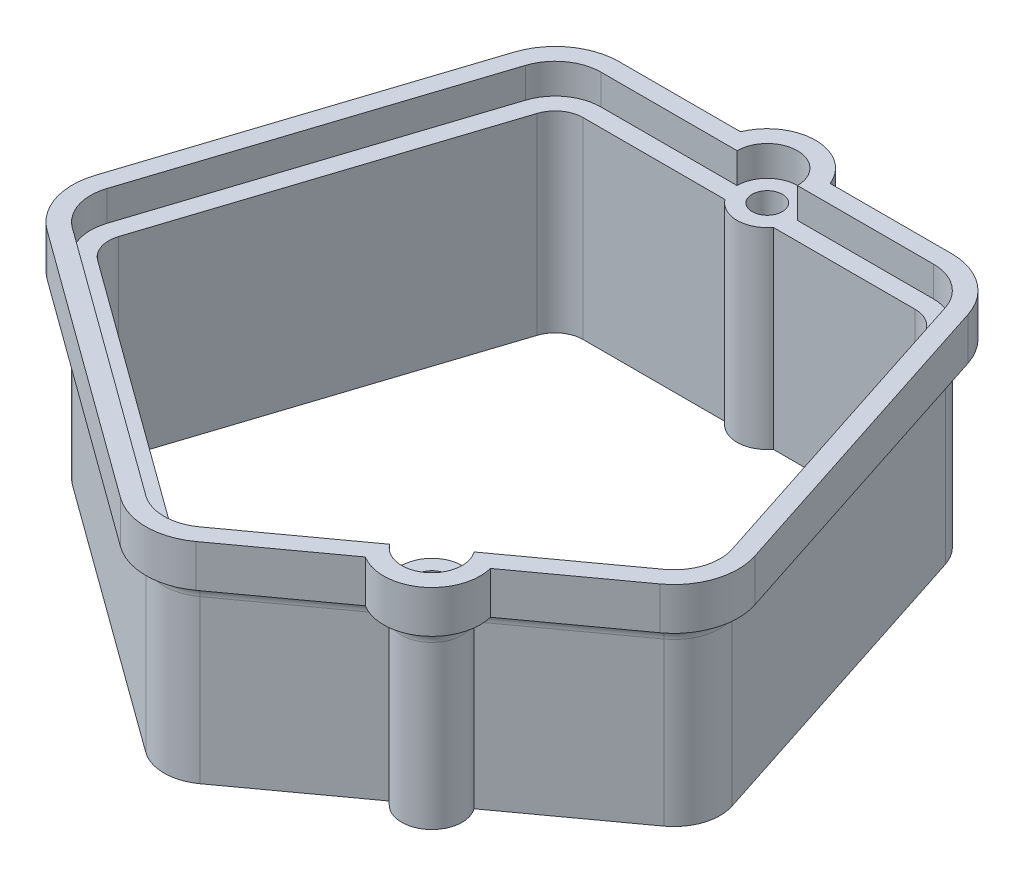
SolidWorks part; units mm, degrees
material "ABS"
ref_plane "Front Plane" through (0, 0, 0) normal (0, 0, 1) x (1, 0, 0)
ref_plane "Top Plane" through (0, 0, 0) normal (0, 1, 0) x (1, 0, 0)
ref_plane "Right Plane" through (0, 0, 0) normal (1, 0, 0) x (0, 0, -1)
sketch "Sketch1" plane through (0, 0, 0) normal (0, 1, 0) x (1, 0, 0)
  line L0 (-42.9604, -16.814) -> (1.5332, -49.1405)
  line L1 (6.9643, -49.1405) -> (25.975, -35.3284)
  line L2 (4.2488, 51.849) -> (4.2488, 50.849)
  line L3 (0.2488, 46.849) -> (-23.2498, 46.849)
  line L4 (-30.4968, 41.5837) -> (-47.4919, -10.7216)
  line L5 (-44.7237, -19.241) -> (-0.2302, -51.5675)
  line L6 (8.7277, -51.5675) -> (27.7384, -37.7554)
  line L7 (33.3256, -38.6403) -> (33.9134, -39.4494)
  line L8 (35.0196, -32.4654) -> (53.2213, -19.241)
  line L9 (55.9894, -10.7216) -> (38.9943, 41.5837)
  line L10 (31.7473, 46.849) -> (9.2488, 46.849)
  line L11 (32.4472, -30.6261) -> (51.4579, -16.814)
  line L12 (53.1362, -11.6487) -> (36.1412, 40.6567)
  line L13 (31.7473, 43.849) -> (8.2488, 43.849)
  line L14 (-23.2498, 43.849) -> (0.2488, 43.849)
  line L15 (-44.6387, -11.6487) -> (-27.6437, 40.6567)
  line L16 (-47.4919, -15.431) -> (47.4919, 15.431) construction
  line L17 (-44.6387, -14.504) -> (44.6387, 14.504) construction
  arc A0 (9.2488, 46.849) -> (4.2488, 51.849) centre (4.2488, 46.849) ccw
  arc A1 (4.2488, 50.849) -> (0.2488, 46.849) centre (4.2488, 46.849) ccw
  arc A2 (-23.2498, 46.849) -> (-30.4968, 41.5837) centre (-23.2498, 39.229) ccw
  arc A3 (-47.4919, -10.7216) -> (-44.7237, -19.241) centre (-40.2448, -13.0763) ccw
  arc A4 (-0.2302, -51.5675) -> (8.7277, -51.5675) centre (4.2488, -45.4028) ccw
  arc A5 (27.7384, -37.7554) -> (33.3256, -38.6403) centre (30.9745, -35.4043) ccw
  arc A6 (33.9134, -39.4494) -> (35.0196, -32.4654) centre (30.9745, -35.4043) ccw
  arc A7 (53.2213, -19.241) -> (55.9894, -10.7216) centre (48.7423, -13.0763) ccw
  arc A8 (38.9943, 41.5837) -> (31.7473, 46.849) centre (31.7473, 39.229) ccw
  arc A9 (-44.6387, -11.6487) -> (-42.9604, -16.814) centre (-40.2448, -13.0763) ccw
  arc A10 (1.5332, -49.1405) -> (6.9643, -49.1405) centre (4.2488, -45.4028) ccw
  circle A11 centre (30.9745, -35.4043) radius 2.5
  arc A12 (32.4472, -30.6261) -> (25.975, -35.3284) centre (30.9745, -35.4043) ccw
  arc A13 (51.4579, -16.814) -> (53.1362, -11.6487) centre (48.7423, -13.0763) ccw
  arc A14 (36.1412, 40.6567) -> (31.7473, 43.849) centre (31.7473, 39.229) ccw
  arc A15 (0.2488, 43.849) -> (8.2488, 43.849) centre (4.2488, 46.849) ccw
  circle A16 centre (4.2488, 46.849) radius 2.5
  arc A17 (-23.2498, 43.849) -> (-27.6437, 40.6567) centre (-23.2498, 39.229) ccw
  arc A36 (4.2488, 51.849) -> (-0.7512, 46.849) centre (4.2488, 46.849) ccw
  arc A37 (33.9134, -39.4494) -> (26.9294, -38.3432) centre (30.9745, -35.4043) cw
  point P58 (0, 0)
  point P60 (0, 0)
extrude "Boss-Extrude1" add sketch "Sketch1" along normal blind 40 contours L9 A8 L10 A0 L2 A1 L3 A2 L4 A3 L5 A4 L6 A5 L7 A6 L8 A7 A17 L14 A15 L13 A14 L12 A13 L11 A12 L1 A10 L0 A9 L15 A16 A11 | A37 L7 A5 L6 | L2 A36 L3 A1 region at (6.7388, 0, -49.339) region at (1.3722, 0, -49.7256) region at (30.3381, 0, 39.4223)
sketch "Sketch2" plane through (0, 40, 0) normal (0, 1, 0) x (1, 0, 0)
  line L1 (-30.4968, 41.5837) -> (-33.35, 42.5108)
  line L2 (-47.4919, -10.7216) -> (-50.345, -9.7946)
  line L3 (-33.35, 42.5108) -> (-50.345, -9.7946)
  line L5 (-23.2498, 46.849) -> (-23.2498, 49.849)
  line L8 (55.9894, -10.7216) -> (38.9943, 41.5837)
  line L9 (31.7473, 46.849) -> (9.2488, 46.849)
  line L10 (-0.7512, 46.849) -> (-23.2498, 46.849)
  line L13 (-30.4968, 41.5837) -> (-47.4919, -10.7216)
  line L21 (-44.7237, -19.241) -> (-0.2302, -51.5675)
  line L22 (8.7277, -51.5675) -> (26.9294, -38.3432)
  line L23 (35.0196, -32.4654) -> (53.2213, -19.241)
  line L24 (55.9894, -10.7216) -> (38.9943, 41.5837)
  line L25 (31.7473, 46.849) -> (9.2488, 46.849)
  line L26 (-0.7512, 46.849) -> (-23.2498, 46.849)
  line L27 (-30.4968, 41.5837) -> (-47.4919, -10.7216)
  line L28 (-44.7237, -19.241) -> (-0.2302, -51.5675)
  line L29 (8.7277, -51.5675) -> (26.9294, -38.3432)
  line L30 (35.0196, -32.4654) -> (53.2213, -19.241)
  line L31 (-23.2498, 49.849) -> (-3.1674, 49.849)
  line L33 (54.9846, -21.6681) -> (38.7377, -33.4722)
  line L34 (10.491, -53.9946) -> (26.738, -42.1905)
  line L35 (-1.9935, -53.9946) -> (-46.4871, -21.6681)
  line L36 (31.7473, 49.849) -> (11.665, 49.849)
  line L37 (41.8475, 42.5108) -> (58.8425, -9.7946)
  arc A0 (-3.1674, 49.849) -> (11.665, 49.849) centre (4.2488, 46.849) cw
  arc A1 (-33.35, 42.5108) -> (-23.2498, 49.849) centre (-23.2498, 39.229) cw
  arc A3 (-50.345, -9.7946) -> (-46.4871, -21.6681) centre (-40.2448, -13.0763) ccw
  arc A5 (41.8475, 42.5108) -> (31.7473, 49.849) centre (31.7473, 39.229) ccw
  arc A6 (58.8425, -9.7946) -> (54.9846, -21.6681) centre (48.7423, -13.0763) cw
  arc A21 (26.738, -42.1905) -> (38.7377, -33.4722) centre (30.9745, -35.4043) ccw
  arc A22 (-1.9935, -53.9946) -> (10.491, -53.9946) centre (4.2488, -45.4028) ccw
  arc A23 (38.9943, 41.5837) -> (31.7473, 46.849) centre (31.7473, 39.229) ccw
  arc A24 (9.2488, 46.849) -> (-0.7512, 46.849) centre (4.2488, 46.849) ccw
  arc A25 (-23.2498, 46.849) -> (-30.4968, 41.5837) centre (-23.2498, 39.229) ccw
  arc A26 (-47.4919, -10.7216) -> (-44.7237, -19.241) centre (-40.2448, -13.0763) ccw
  arc A27 (-0.2302, -51.5675) -> (8.7277, -51.5675) centre (4.2488, -45.4028) ccw
  arc A28 (26.9294, -38.3432) -> (35.0196, -32.4654) centre (30.9745, -35.4043) ccw
  arc A29 (53.2213, -19.241) -> (55.9894, -10.7216) centre (48.7423, -13.0763) ccw
  arc A30 (38.9943, 41.5837) -> (31.7473, 46.849) centre (31.7473, 39.229) ccw
  arc A31 (9.2488, 46.849) -> (-0.7512, 46.849) centre (4.2488, 46.849) ccw
  arc A32 (-23.2498, 46.849) -> (-30.4968, 41.5837) centre (-23.2498, 39.229) ccw
  arc A33 (-47.4919, -10.7216) -> (-44.7237, -19.241) centre (-40.2448, -13.0763) ccw
  arc A34 (-0.2302, -51.5675) -> (8.7277, -51.5675) centre (4.2488, -45.4028) ccw
  arc A35 (26.9294, -38.3432) -> (35.0196, -32.4654) centre (30.9745, -35.4043) ccw
  arc A36 (53.2213, -19.241) -> (55.9894, -10.7216) centre (48.7423, -13.0763) ccw
  line M62 (55.9894, -10.7216) -> (38.9943, 41.5837)
  arc M63 (38.9943, 41.5837) -> (31.7473, 46.849) centre (31.7473, 39.229) ccw
  line M64 (31.7473, 46.849) -> (9.2488, 46.849)
  arc M65 (9.2488, 46.849) -> (-0.7512, 46.849) centre (4.2488, 46.849) ccw
  line M66 (-0.7512, 46.849) -> (-23.2498, 46.849)
  arc M67 (-23.2498, 46.849) -> (-30.4968, 41.5837) centre (-23.2498, 39.229) ccw
  line M68 (-30.4968, 41.5837) -> (-47.4919, -10.7216)
  arc M69 (-47.4919, -10.7216) -> (-44.7237, -19.241) centre (-40.2448, -13.0763) ccw
  line M70 (-44.7237, -19.241) -> (-0.2302, -51.5675)
  arc M71 (-0.2302, -51.5675) -> (8.7277, -51.5675) centre (4.2488, -45.4028) ccw
  line M72 (8.7277, -51.5675) -> (26.9294, -38.3432)
  arc M73 (26.9294, -38.3432) -> (35.0196, -32.4654) centre (30.9745, -35.4043) ccw
  line M74 (35.0196, -32.4654) -> (53.2213, -19.241)
  arc M75 (53.2213, -19.241) -> (55.9894, -10.7216) centre (48.7423, -13.0763) ccw
  dimension "D5" = 3
  dimension "D2" = 3
  dimension "D3" = 3
  dimension "D1" = 0
extrude "Boss-Extrude2" add sketch "Sketch2" along normal blind 5 and the other way blind 2 contours L1 L3 L2 M68 | L35 A22 L34 A21 L33 A6 L37 A5 L36 A0 L31 L5 L2 A3 M66 M65 M64 M63 M62 M75 M74 M73 M72 M71 M70 M69 | A1 L1 L5 M67 region at (-40.4209, 40, -15.8946) region at (-28.3098, 40, -46.1935) region at (-48.9788, 40, 15.9142)
fillet "Fillet1" radius 3 14 edges at (20.498, 38, -46.849) (36.2262, 38, -45.3937) (47.4919, 38, -15.431) (55.9894, 38, 15.431) (-12.0005, 38, -46.849) (-27.7287, 38, -45.3937) (-38.9943, 38, -15.431) (-47.4919, 38, 15.431) (17.8285, 38, 44.9554) (4.2488, 38, 53.0228) (4.2488, 38, -51.849) (33.9134, 38, 39.4494) (44.1204, 38, 25.8532) (-22.477, 38, 35.4043)
sketch "Sketch3" plane through (0, 0, 0) normal (0, -1, 0) x (1, 0, 0)
  line L7 (-44.6387, 11.6487) -> (-27.6437, -40.6567)
  line L8 (1.5332, 49.1405) -> (-42.9604, 16.814)
  line L9 (25.975, 35.3284) -> (6.9643, 49.1405)
  line L10 (51.4579, 16.814) -> (32.4472, 30.6261)
  line L11 (36.1412, -40.6567) -> (53.1362, 11.6487)
  line L12 (8.2488, -43.849) -> (31.7473, -43.849)
  line L13 (-23.2498, -43.849) -> (0.2488, -43.849)
  line L14 (-44.6387, 11.6487) -> (-27.6437, -40.6567)
  line L15 (1.5332, 49.1405) -> (-42.9604, 16.814)
  line L16 (25.975, 35.3284) -> (6.9643, 49.1405)
  line L17 (51.4579, 16.814) -> (32.4472, 30.6261)
  line L18 (36.1412, -40.6567) -> (53.1362, 11.6487)
  line L19 (8.2488, -43.849) -> (31.7473, -43.849)
  line L20 (-23.2498, -43.849) -> (0.2488, -43.849)
  line L21 (38.9943, -41.5837) -> (55.9894, 10.7216)
  line L22 (53.2213, 19.241) -> (35.0196, 32.4654)
  line L23 (26.9294, 38.3432) -> (8.7277, 51.5675)
  line L24 (-0.2302, 51.5675) -> (-44.7237, 19.241)
  line L25 (-47.4919, 10.7216) -> (-30.4968, -41.5837)
  line L26 (-23.2498, -46.849) -> (-0.7512, -46.849)
  line L27 (9.2488, -46.849) -> (31.7473, -46.849)
  line L28 (38.9943, -41.5837) -> (55.9894, 10.7216)
  line L29 (53.2213, 19.241) -> (35.0196, 32.4654)
  line L30 (26.9294, 38.3432) -> (8.7277, 51.5675)
  line L31 (-0.2302, 51.5675) -> (-44.7237, 19.241)
  line L32 (-47.4919, 10.7216) -> (-30.4968, -41.5837)
  line L33 (-23.2498, -46.849) -> (-0.7512, -46.849)
  line L34 (9.2488, -46.849) -> (31.7473, -46.849)
  circle A1 centre (30.9745, 35.4043) radius 2.5
  circle A2 centre (30.9745, 35.4043) radius 2.5
  circle A3 centre (4.2488, -46.849) radius 2.5
  circle A4 centre (4.2488, -46.849) radius 2.5
  arc A7 (-27.6437, -40.6567) -> (-23.2498, -43.849) centre (-23.2498, -39.229) ccw
  arc A8 (-42.9604, 16.814) -> (-44.6387, 11.6487) centre (-40.2448, 13.0763) ccw
  arc A9 (6.9643, 49.1405) -> (1.5332, 49.1405) centre (4.2488, 45.4028) ccw
  arc A10 (25.975, 35.3284) -> (32.4472, 30.6261) centre (30.9745, 35.4043) ccw
  arc A11 (53.1362, 11.6487) -> (51.4579, 16.814) centre (48.7423, 13.0763) ccw
  arc A12 (31.7473, -43.849) -> (36.1412, -40.6567) centre (31.7473, -39.229) ccw
  arc A13 (8.2488, -43.849) -> (0.2488, -43.849) centre (4.2488, -46.849) ccw
  arc A14 (-27.6437, -40.6567) -> (-23.2498, -43.849) centre (-23.2498, -39.229) ccw
  arc A15 (-42.9604, 16.814) -> (-44.6387, 11.6487) centre (-40.2448, 13.0763) ccw
  arc A16 (6.9643, 49.1405) -> (1.5332, 49.1405) centre (4.2488, 45.4028) ccw
  arc A17 (25.975, 35.3284) -> (32.4472, 30.6261) centre (30.9745, 35.4043) ccw
  arc A18 (53.1362, 11.6487) -> (51.4579, 16.814) centre (48.7423, 13.0763) ccw
  arc A19 (31.7473, -43.849) -> (36.1412, -40.6567) centre (31.7473, -39.229) ccw
  arc A20 (8.2488, -43.849) -> (0.2488, -43.849) centre (4.2488, -46.849) ccw
  arc A25 (55.9894, 10.7216) -> (53.2213, 19.241) centre (48.7423, 13.0763) ccw
  arc A26 (35.0196, 32.4654) -> (26.9294, 38.3432) centre (30.9745, 35.4043) ccw
  arc A27 (8.7277, 51.5675) -> (-0.2302, 51.5675) centre (4.2488, 45.4028) ccw
  arc A28 (-44.7237, 19.241) -> (-47.4919, 10.7216) centre (-40.2448, 13.0763) ccw
  arc A29 (-30.4968, -41.5837) -> (-23.2498, -46.849) centre (-23.2498, -39.229) ccw
  arc A30 (-0.7512, -46.849) -> (9.2488, -46.849) centre (4.2488, -46.849) ccw
  arc A31 (31.7473, -46.849) -> (38.9943, -41.5837) centre (31.7473, -39.229) ccw
  arc A32 (55.9894, 10.7216) -> (53.2213, 19.241) centre (48.7423, 13.0763) ccw
  arc A33 (35.0196, 32.4654) -> (26.9294, 38.3432) centre (30.9745, 35.4043) ccw
  arc A34 (8.7277, 51.5675) -> (-0.2302, 51.5675) centre (4.2488, 45.4028) ccw
  arc A35 (-44.7237, 19.241) -> (-47.4919, 10.7216) centre (-40.2448, 13.0763) ccw
  arc A36 (-30.4968, -41.5837) -> (-23.2498, -46.849) centre (-23.2498, -39.229) ccw
  arc A37 (-0.7512, -46.849) -> (9.2488, -46.849) centre (4.2488, -46.849) ccw
  arc A38 (31.7473, -46.849) -> (38.9943, -41.5837) centre (31.7473, -39.229) ccw
  dimension "D1" = 0
  dimension "D2" = 0
  dimension "D3" = 0
  dimension "D4" = 0
extrude "Boss-Extrude3" add sketch "Sketch3" along normal blind 7
sketch "Sketch4" plane through (0, -7, 0) normal (0, -1, 0) x (1, 0, 0)
  line L7 (-23.2498, -43.849) -> (0.2488, -43.849)
  line L8 (-44.6387, 11.6487) -> (-27.6437, -40.6567)
  line L9 (1.5332, 49.1405) -> (-42.9604, 16.814)
  line L10 (25.975, 35.3284) -> (6.9643, 49.1405)
  line L11 (51.4579, 16.814) -> (32.4472, 30.6261)
  line L12 (36.1412, -40.6567) -> (53.1362, 11.6487)
  line L13 (8.2488, -43.849) -> (31.7473, -43.849)
  line L14 (-23.2498, -43.849) -> (0.2488, -43.849)
  line L15 (-44.6387, 11.6487) -> (-27.6437, -40.6567)
  line L16 (1.5332, 49.1405) -> (-42.9604, 16.814)
  line L17 (25.975, 35.3284) -> (6.9643, 49.1405)
  line L18 (51.4579, 16.814) -> (32.4472, 30.6261)
  line L19 (36.1412, -40.6567) -> (53.1362, 11.6487)
  line L20 (8.2488, -43.849) -> (31.7473, -43.849)
  line L21 (38.9943, -41.5837) -> (55.9894, 10.7216)
  line L22 (53.2213, 19.241) -> (35.0196, 32.4654)
  line L23 (26.9294, 38.3432) -> (8.7277, 51.5675)
  line L24 (-0.2302, 51.5675) -> (-44.7237, 19.241)
  line L25 (-47.4919, 10.7216) -> (-30.4968, -41.5837)
  line L26 (-23.2498, -46.849) -> (-0.7512, -46.849)
  line L27 (9.2488, -46.849) -> (31.7473, -46.849)
  line L28 (38.9943, -41.5837) -> (55.9894, 10.7216)
  line L29 (53.2213, 19.241) -> (35.0196, 32.4654)
  line L30 (26.9294, 38.3432) -> (8.7277, 51.5675)
  line L31 (-0.2302, 51.5675) -> (-44.7237, 19.241)
  line L32 (-47.4919, 10.7216) -> (-30.4968, -41.5837)
  line L33 (-23.2498, -46.849) -> (-0.7512, -46.849)
  line L34 (9.2488, -46.849) -> (31.7473, -46.849)
  circle A1 centre (30.9745, 35.4043) radius 2.5
  circle A2 centre (30.9745, 35.4043) radius 2.5
  circle A3 centre (4.2488, -46.849) radius 2.5
  circle A4 centre (4.2488, -46.849) radius 2.5
  arc A7 (-27.6437, -40.6567) -> (-23.2498, -43.849) centre (-23.2498, -39.229) ccw
  arc A8 (-42.9604, 16.814) -> (-44.6387, 11.6487) centre (-40.2448, 13.0763) ccw
  arc A9 (6.9643, 49.1405) -> (1.5332, 49.1405) centre (4.2488, 45.4028) ccw
  arc A10 (25.975, 35.3284) -> (32.4472, 30.6261) centre (30.9745, 35.4043) ccw
  arc A11 (53.1362, 11.6487) -> (51.4579, 16.814) centre (48.7423, 13.0763) ccw
  arc A12 (31.7473, -43.849) -> (36.1412, -40.6567) centre (31.7473, -39.229) ccw
  arc A13 (8.2488, -43.849) -> (0.2488, -43.849) centre (4.2488, -46.849) ccw
  arc A14 (-27.6437, -40.6567) -> (-23.2498, -43.849) centre (-23.2498, -39.229) ccw
  arc A15 (-42.9604, 16.814) -> (-44.6387, 11.6487) centre (-40.2448, 13.0763) ccw
  arc A16 (6.9643, 49.1405) -> (1.5332, 49.1405) centre (4.2488, 45.4028) ccw
  arc A17 (25.975, 35.3284) -> (32.4472, 30.6261) centre (30.9745, 35.4043) ccw
  arc A18 (53.1362, 11.6487) -> (51.4579, 16.814) centre (48.7423, 13.0763) ccw
  arc A19 (31.7473, -43.849) -> (36.1412, -40.6567) centre (31.7473, -39.229) ccw
  arc A20 (8.2488, -43.849) -> (0.2488, -43.849) centre (4.2488, -46.849) ccw
  arc A25 (31.7473, -46.849) -> (38.9943, -41.5837) centre (31.7473, -39.229) ccw
  arc A26 (55.9894, 10.7216) -> (53.2213, 19.241) centre (48.7423, 13.0763) ccw
  arc A27 (35.0196, 32.4654) -> (26.9294, 38.3432) centre (30.9745, 35.4043) ccw
  arc A28 (8.7277, 51.5675) -> (-0.2302, 51.5675) centre (4.2488, 45.4028) ccw
  arc A29 (-44.7237, 19.241) -> (-47.4919, 10.7216) centre (-40.2448, 13.0763) ccw
  arc A30 (-30.4968, -41.5837) -> (-23.2498, -46.849) centre (-23.2498, -39.229) ccw
  arc A31 (-0.7512, -46.849) -> (9.2488, -46.849) centre (4.2488, -46.849) ccw
  arc A32 (31.7473, -46.849) -> (38.9943, -41.5837) centre (31.7473, -39.229) ccw
  arc A33 (55.9894, 10.7216) -> (53.2213, 19.241) centre (48.7423, 13.0763) ccw
  arc A34 (35.0196, 32.4654) -> (26.9294, 38.3432) centre (30.9745, 35.4043) ccw
  arc A35 (8.7277, 51.5675) -> (-0.2302, 51.5675) centre (4.2488, 45.4028) ccw
  arc A36 (-44.7237, 19.241) -> (-47.4919, 10.7216) centre (-40.2448, 13.0763) ccw
  arc A37 (-30.4968, -41.5837) -> (-23.2498, -46.849) centre (-23.2498, -39.229) ccw
  arc A38 (-0.7512, -46.849) -> (9.2488, -46.849) centre (4.2488, -46.849) ccw
  dimension "D1" = 0
  dimension "D2" = 0
  dimension "D3" = 0
  dimension "D4" = 0
extrude "Cut-Extrude1" cut sketch "Sketch4" against normal blind 15.17
